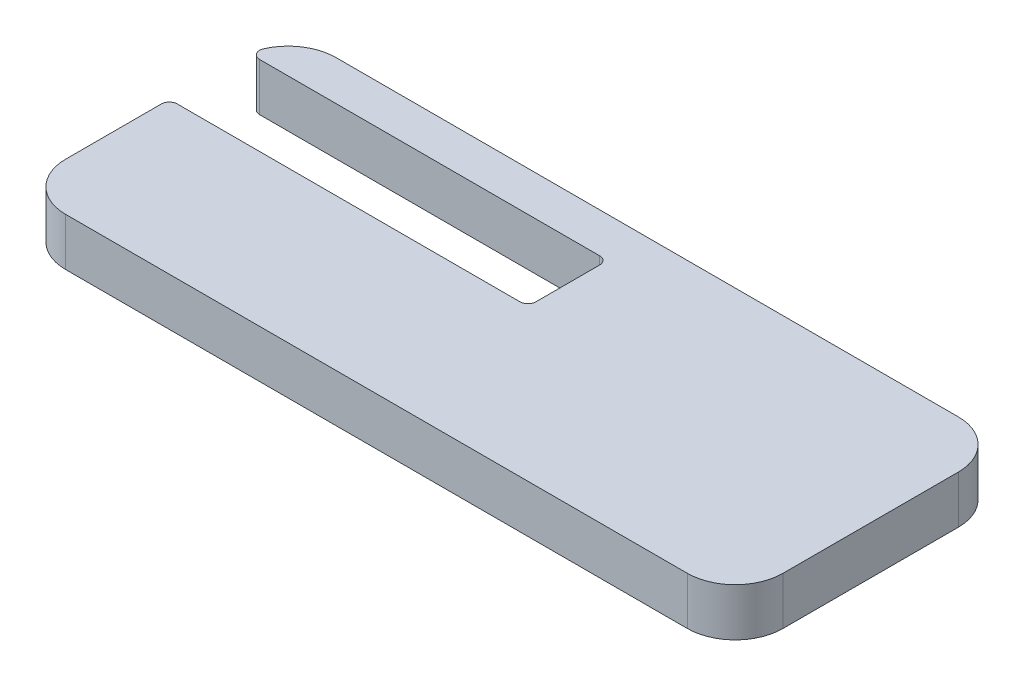
SolidWorks part; units mm, degrees
ref_plane "Alzado" through (0, 0, 0) normal (0, 0, 1) x (1, 0, 0)
ref_plane "Planta" through (0, 0, 0) normal (0, 1, 0) x (1, 0, 0)
ref_plane "Vista lateral" through (0, 0, 0) normal (1, 0, 0) x (0, 0, -1)
sketch "Croquis1" plane through (0, 0, 0) normal (0, 1, 0) x (1, 0, 0)
  line L5 (-22.5, 9.9298) -> (22.5, 9.9298)
  line L6 (-22.5, 9.9298) -> (-22.5, -7.0702)
  line L7 (-22.5, -7.0702) -> (22.5, -7.0702)
  line L8 (22.5, 9.9298) -> (22.5, -7.0702)
  dimension "D1" = 9.9298
  dimension "D2" = 22.5
  dimension "D3" = 17
  dimension "D4" = 45
extrude "Saliente-Extruir1" add sketch "Croquis1" along normal blind 3
sketch "Croquis2" plane through (0, 3, 0) normal (0, 1, 0) x (1, 0, 0)
  line L0 (-22.5, 9.9298) -> (-22.5, -7.0702) construction
  line L1 (-22.5, 7.4298) -> (0, 7.4298)
  line L2 (-22.5, 7.4298) -> (-22.5, 2.4298)
  line L3 (-22.5, 2.4298) -> (0, 2.4298)
  line L4 (0, 7.4298) -> (0, 2.4298)
  line L6 (22.5, 9.9298) -> (-22.5, 9.9298) construction
  dimension "D1" = 22.5
  dimension "D2" = 2.5
  dimension "D3" = 5
extrude "Cortar-Extruir1" cut sketch "Croquis2" against normal up to surface (3 mm away) up to face at (0, 0, -1.4298)
fillet "Redondeo1" radius 3 4 edges at (-22.5, 1.5, 7.0702) (-22.5, 1.5, -9.9298) (22.5, 1.5, 7.0702) (22.5, 1.5, -9.9298)
fillet "Redondeo4" radius 0.5 4 edges at (-22.5, 1.5, -2.4298) (0, 1.5, -2.4298) (0, 1.5, -7.4298) (-22.5, 1.5, -7.4298)
